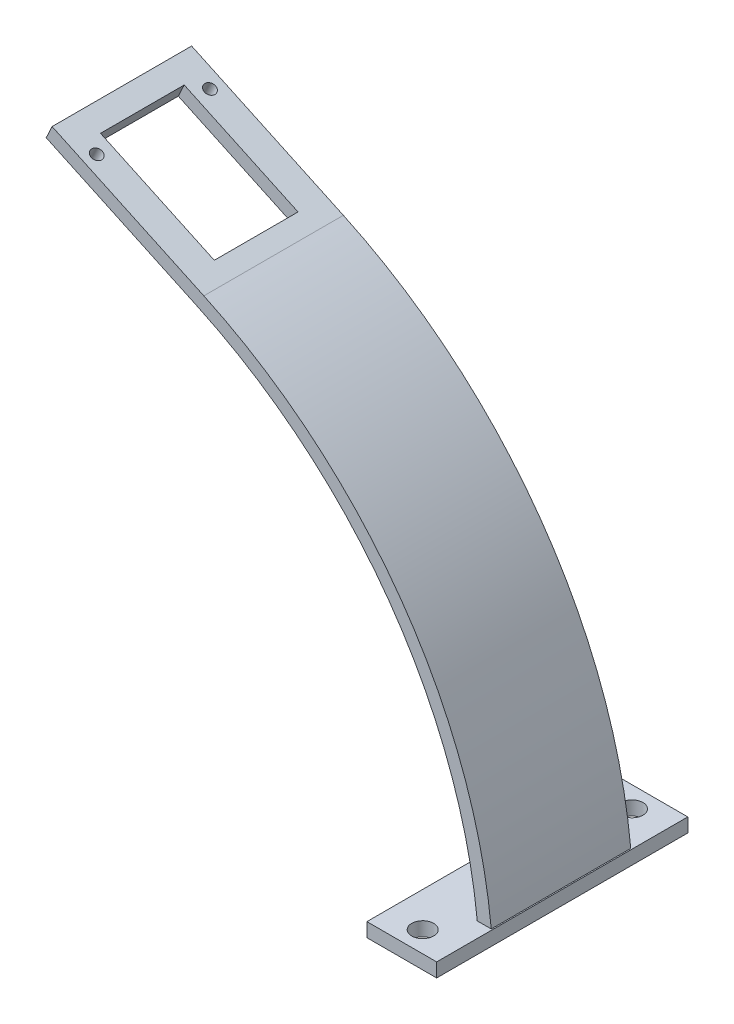
SolidWorks part; units mm, degrees
ref_plane "Front" through (0, 0, 0) normal (0, 0, 1) x (1, 0, 0)
ref_plane "Top" through (0, 0, 0) normal (0, 1, 0) x (1, 0, 0)
ref_plane "Right" through (0, 0, 0) normal (1, 0, 0) x (0, 0, -1)
sketch "Sketch1" plane through (0, 0, 0) normal (0, 0, 1) x (1, 0, 0)
  line L0 (-51.0785, 73.898) -> (-78.7027, 86.7794)
  line L1 (-78.7027, 86.7794) -> (-77.6293, 89.0814)
  line L2 (-77.6293, 89.0814) -> (-50.005, 76.2)
  line L3 (0, 0) -> (2.54, 0)
  line L4 (55, 0) -> (-55, 0) construction
  arc A0 (0, 0) -> (-51.0785, 73.898) centre (-88.6492, -6.6728) ccw
  arc A1 (-50.005, 76.2) -> (2.54, 0) centre (-88.6435, -6.6605) cw
  dimension "D3" = 88.9
  dimension "D4" = 25
  dimension "D1" = 2.54
  dimension "D2" = 2.54
  dimension "D5" = 30.48
  dimension "D6" = 30.48
  dimension "D7" = 76.2
extrude "Boss-Extrude1" add sketch "Sketch1" along normal blind 25.4
sketch "Sketch2" plane through (20.2551, 43.4372, 0) normal (0.4226, 0.9063, 0) x (0.9063, -0.4226, 0)
  line L0 (-108.0034, -25.4) -> (-108.0034, 0) construction
  line L1 (-103.8886, -5.08) -> (-81.0286, -5.08)
  line L2 (-103.8886, -5.08) -> (-103.8886, -20.32)
  line L3 (-103.8886, -20.32) -> (-81.0286, -20.32)
  line L4 (-81.0286, -5.08) -> (-81.0286, -20.32)
  line L5 (-108.0034, 0) -> (-108.0034, -25.4) construction
  line L6 (-55, 0) -> (55, 0) construction
  line L7 (-108.0034, -12.7) -> (-81.0286, -12.7) construction
  line L8 (-77.5234, -25.4) -> (-108.0034, -25.4) construction
  circle A0 centre (-101.6534, -2.4168) radius 0.9995
  circle A1 centre (-101.6534, -23.034) radius 0.9995
  point P12 (-108.0034, -12.7)
  point P13 (-103.8886, -12.7)
  dimension "D4" = 1.999
  dimension "D6" = 20.6172
  dimension "D7" = 6.35
  dimension "D1" = 22.86
  dimension "D2" = 15.24
  dimension "D3" = 4.1148
  dimension "D5" = 2.366
extrude "Cut-Extrude1" cut sketch "Sketch2" against normal up to next
sketch "Sketch3" plane through (0, 0, 0) normal (0, 1, 0) x (1, 0, 0)
  line L0 (-55, 0) -> (55, 0) construction
  line L1 (2.54, -35.56) -> (-10.16, -35.56)
  line L2 (2.54, -35.56) -> (2.54, 10.16)
  line L3 (2.54, 10.16) -> (-10.16, 10.16)
  line L4 (-10.16, -35.56) -> (-10.16, 10.16)
  line L5 (-50.005, -25.4) -> (2.54, -25.4) construction
  line L6 (2.54, -25.4) -> (2.54, 0) construction
  circle A0 centre (-3.81, 6.35) radius 2
  circle A1 centre (-3.81, -31.75) radius 2
  dimension "D1" = 4
  dimension "D2" = 4
  dimension "D5" = 6.35
  dimension "D3" = 38.1
  dimension "D4" = 6.35
  dimension "D6" = 10.16
  dimension "D7" = 10.16
  dimension "D8" = 12.7
extrude "Boss-Extrude2" add sketch "Sketch3" along normal blind 2.54
